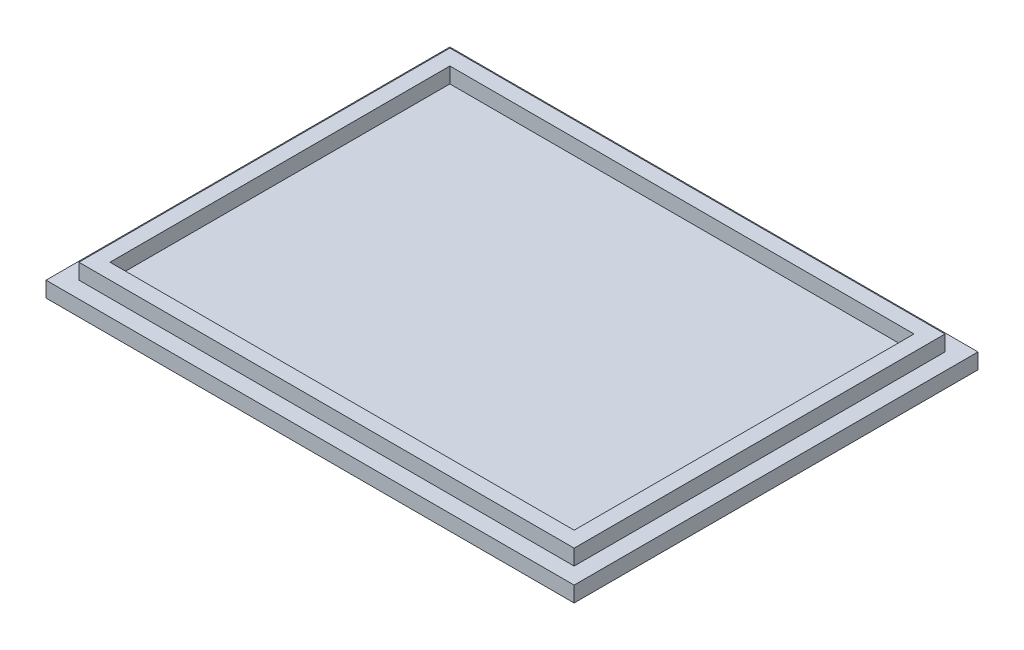
SolidWorks part; units mm, degrees
ref_plane "前视基准面" through (0, 0, 0) normal (0, 0, 1) x (1, 0, 0)
ref_plane "上视基准面" through (0, 0, 0) normal (0, 1, 0) x (1, 0, 0)
ref_plane "右视基准面" through (0, 0, 0) normal (1, 0, 0) x (0, 0, -1)
sketch "草图1" plane through (0, 0, 0) normal (0, 1, 0) x (1, 0, 0)
  line L1 (-42.5, -32.5) -> (42.5, -32.5)
  line L2 (-42.5, -32.5) -> (-42.5, 32.5)
  line L3 (-42.5, 32.5) -> (42.5, 32.5)
  line L4 (42.5, -32.5) -> (42.5, 32.5)
  line L5 (-42.5, -32.5) -> (42.5, 32.5) construction
  line L6 (-42.5, 32.5) -> (42.5, -32.5) construction
  point P0 (0, 0)
  dimension "D1" = 85
  dimension "D2" = 65
extrude "凸台-拉伸1" add sketch "草图1" along normal blind 2.5
sketch "草图3" plane through (0, 2.5, 0) normal (0, 1, 0) x (1, 0, 0)
  line L1 (-39.85, -29.85) -> (39.85, -29.85)
  line L2 (-39.85, -29.85) -> (-39.85, 29.85)
  line L3 (-39.85, 29.85) -> (39.85, 29.85)
  line L4 (39.85, -29.85) -> (39.85, 29.85)
  line L5 (-39.85, -29.85) -> (39.85, 29.85) construction
  line L6 (-39.85, 29.85) -> (39.85, -29.85) construction
  point P0 (0, 0)
  dimension "D1" = 79.7
  dimension "D2" = 59.7
extrude "凸台-拉伸2" add sketch "草图3" along normal blind 2.5
shell "抽壳1" thickness 2.5 removed face at (0, 5, 0)
